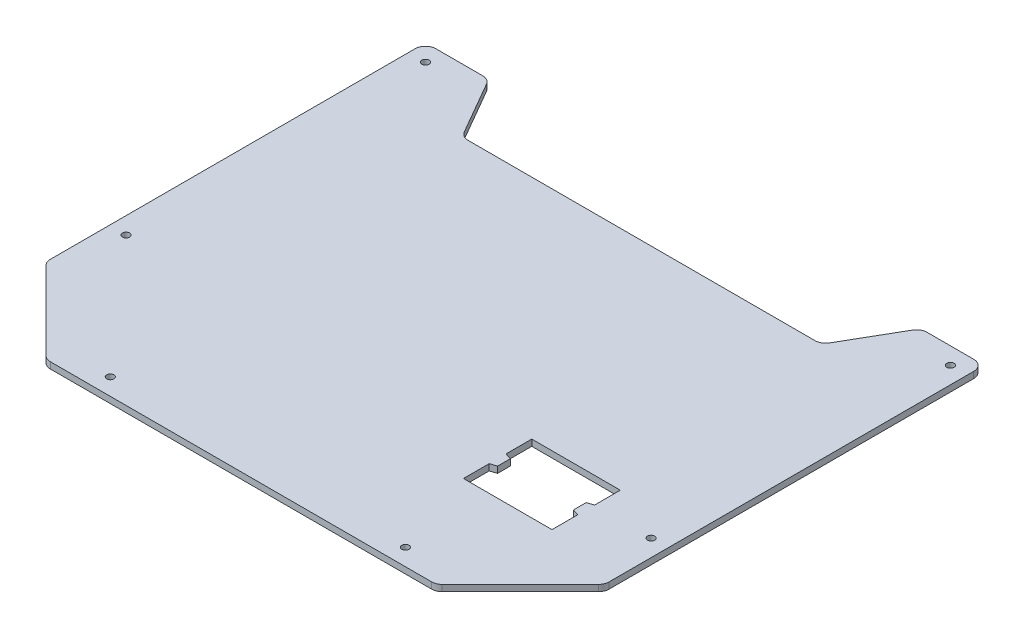
SolidWorks part; units mm, degrees
material "Acier non allié"
ref_plane "Front" through (0, 0, 0) normal (0, 0, 1) x (1, 0, 0)
ref_plane "Top" through (0, 0, 0) normal (0, 1, 0) x (1, 0, 0)
ref_plane "Right" through (0, 0, 0) normal (1, 0, 0) x (0, 0, -1)
sketch "Esquisse1" plane through (0, 0, 0) normal (0, 1, 0) x (1, 0, 0)
  line L0 (0, 0) -> (0, 1919.0564) construction
  line L1 (-92.5, 0) -> (92.5, 0)
  line L2 (92.5, 0) -> (132.5, 40)
  line L3 (132.5, 40) -> (132.5, 220)
  line L4 (132.5, 220) -> (102.5, 220)
  line L5 (102.5, 220) -> (85.1795, 190)
  line L6 (85.1795, 190) -> (-85.1795, 190)
  line L7 (-102.5, 220) -> (-85.1795, 190)
  line L8 (-132.5, 220) -> (-102.5, 220)
  line L9 (-132.5, 40) -> (-132.5, 220)
  line L10 (-92.5, 0) -> (-132.5, 40)
  point P9 (0, 0)
  point P11 (157.045, -28.4591)
  point P12 (0, 190)
  dimension "D1" = 132.5
  dimension "D2" = 220
  dimension "D3" = 30
  dimension "D4" = 30
  dimension "D5" = 40
  dimension "D6" = 40
  dimension "D7" = 60
extrude "Boss.-Extru.1" add sketch "Esquisse1" along normal blind 3
fillet "Congé1" radius 5 10 edges at (132.5, 1.5, -220) (102.5, 1.5, -220) (85.1795, 1.5, -190) (-85.1795, 1.5, -190) (-102.5, 1.5, -220) (-132.5, 1.5, -220) (-132.5, 1.5, -40) (-92.5, 1.5, 0) (92.5, 1.5, 0) (132.5, 1.5, -40)
sketch "Esquisse2" plane through (0, 0, 0) normal (0, -1, 0) x (1, 0, 0)
  line L0 (0, 0) -> (0, -330.9968) construction
  line L1 (-90.4289, 0) -> (90.4289, 0) construction
  line L2 (-105.3868, -220) -> (-127.5, -220) construction
  line L3 (-132.5, -215) -> (-132.5, -42.0711) construction
  circle A0 centre (-70, -8) radius 1
  circle A1 centre (-124.5, -70) radius 1
  circle A2 centre (-124.5, -212) radius 1
  circle A3 centre (124.5, -212) radius 1
  circle A4 centre (124.5, -70) radius 1
  circle A5 centre (70, -8) radius 1
  dimension "D3" = 2
  dimension "D6" = 2
  dimension "D9" = 2
  dimension "D1" = 70
  dimension "D2" = 8
  dimension "D4" = 124.5
  dimension "D5" = 70
  dimension "D7" = 8
  dimension "D8" = 8
extrude "Enlèv. mat.-Extru.1" cut sketch "Esquisse2" against normal through all
hole_wizard "Dégagement M31" positions "Esquisse3" profile "Esquisse4" hole size "M3" standard "ISO" end condition through all
sketch "Esquisse3" plane through (0, 0, 0) normal (0, -1, 0) x (-1, 0, 0)
  point P0 (-70, 8)
  point P3 (-124.5, 70)
  point P6 (-124.5, 212)
  point P9 (124.5, 212)
  point P12 (124.5, 70)
  point P15 (70, 8)
sketch "Esquisse4" plane through (70, 0, -8) normal (1, 0, 0) x (0, 0, -1)
  line L0 (0, 0) -> (0, 3)
  line L1 (0, 3) -> (1.7, 3)
  line L2 (1.7, 3) -> (1.7, 0)
  line L5 (1.7, 0) -> (0, 0)
  line L11 (0, -6.35) -> (0, 107.95) construction
  dimension "Diamètre du perçage jusqu'au prochain" = 3.4
  dimension "Profondeur du perçage jusqu'au prochain" = 3
sketch "Esquisse5" plane through (0, 0, 0) normal (0, -1, 0) x (1, 0, 0)
  line L0 (132.5, -42.0711) -> (132.5, -215) construction
  line L1 (97.5, -82.4) -> (55.5, -82.4) construction
  line L2 (97.5, -82.4) -> (97.5, -50) construction
  line L3 (97.5, -50) -> (55.5, -50) construction
  line L4 (55.5, -82.4) -> (55.5, -50) construction
  line L5 (-90.4289, 0) -> (90.4289, 0) construction
  line L6 (76.5, -82.4) -> (76.5, -41.1293) construction
  line L7 (97.5, -66.2) -> (27.496, -66.2) construction
  line L8 (97.5, -50) -> (55.5, -50)
  line L9 (55.5, -50) -> (55.5, -62.2)
  line L10 (55.5, -62.2) -> (58.5, -63.2)
  line L11 (58.5, -63.2) -> (58.5, -69.2)
  line L12 (94.5, -63.2) -> (94.5, -69.2)
  line L13 (97.5, -62.2) -> (94.5, -63.2)
  line L14 (97.5, -50) -> (97.5, -62.2)
  line L15 (55.5, -70.2) -> (58.5, -69.2)
  line L16 (55.5, -82.4) -> (55.5, -70.2)
  line L17 (97.5, -82.4) -> (55.5, -82.4)
  line L18 (97.5, -70.2) -> (94.5, -69.2)
  line L19 (97.5, -82.4) -> (97.5, -70.2)
  point P12 (0, 0)
  point P19 (76.5, -50)
  point P21 (58.5, -66.2)
  point P23 (94.5, -66.2)
  dimension "D1" = 32.4
  dimension "D2" = 42
  dimension "D3" = 35
  dimension "D4" = 50
  dimension "D5" = 3
  dimension "D6" = 3
  dimension "D7" = 4
extrude "Enlèv. mat.-Extru.2" cut sketch "Esquisse5" against normal through all
equation "\"WIDTH\"= 300mm'Total width of the robot"
equation "\"LENGTH\"= 220mm'Total length of the robot"
equation "\"CUT_DEPTH\"= 45mm'Depth of the cut on the edges of the plate"
equation "\"Plate_th\"= 3mm'Thickness of the plate"
equation "\"D1\"= \"Plate_th\""
